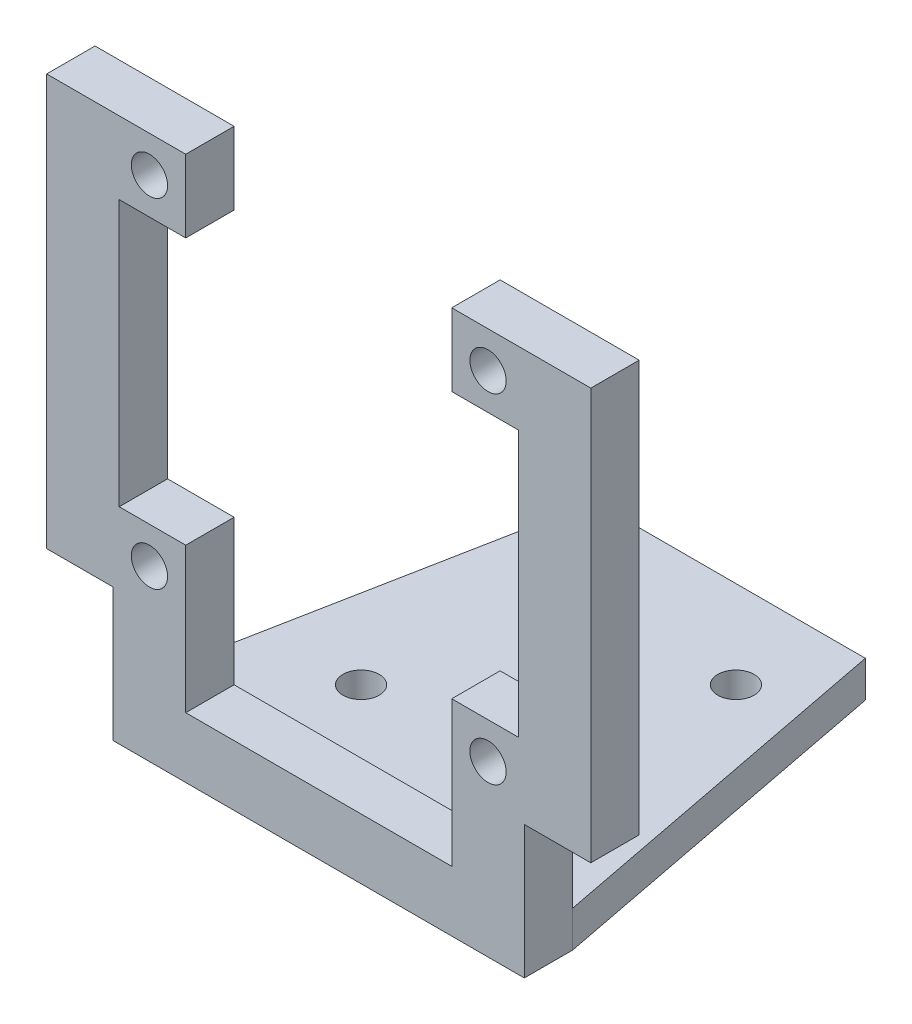
SolidWorks part; units mm, degrees
material "Polyetheretherketone (PEEK)"
ref_plane "Front Plane" through (0, 0, 0) normal (0, 0, 1) x (1, 0, 0)
ref_plane "Top Plane" through (0, 0, 0) normal (0, 1, 0) x (1, 0, 0)
ref_plane "Right Plane" through (0, 0, 0) normal (1, 0, 0) x (0, 0, -1)
sketch "Sketch1" plane through (0, 0, 0) normal (0, 0, 1) x (1, 0, 0)
  line L0 (0, 0) -> (0, 95.25) construction
  line L1 (0, 0) -> (110.5692, 0) construction
  line L2 (11, 17) -> (17, 17)
  line L3 (-17, 17) -> (-11, 17)
  line L4 (-17, 17) -> (-17, -28)
  line L5 (-17, -28) -> (17, -28)
  line L6 (17, 17) -> (17, -28)
  line L12 (-11, 17) -> (-11, -23)
  line L13 (-11, -23) -> (11, -23)
  line L14 (11, 17) -> (11, -23)
  circle A0 centre (-14, 14) radius 1.5
  circle A1 centre (14, 14) radius 1.5
  circle A2 centre (14, -14) radius 1.5
  circle A3 centre (-14, -14) radius 1.5
  dimension "D3" = 3
  dimension "D1" = 34
  dimension "D2" = 45
  dimension "D4" = 28
  dimension "D5" = 14
  dimension "D6" = 28
  dimension "D7" = 5
  dimension "D8" = 22
  dimension "D9" = 14
  dimension "D10" = 28
extrude "Boss-Extrude1" add sketch "Sketch1" along normal blind 4
sketch "Sketch2" plane through (0, 0, 0) normal (0, 0, -1) x (-1, 0, 0)
  line L0 (-17, -28) -> (-17, 17) construction
  line L1 (17, -28) -> (-17, -28)
  line L2 (17, -28) -> (17, -25)
  line L3 (17, -25) -> (-17, -25)
  line L4 (-17, -28) -> (-17, -25)
  dimension "D1" = 3
extrude "Boss-Extrude2" add sketch "Sketch2" along normal blind 30
sketch "Sketch3" plane through (0, -25, 0) normal (0, 1, 0) x (1, 0, 0)
  line L0 (0, 0) -> (0, 39.3383) construction
  line L1 (-17, 15) -> (13.9003, 15) construction
  line L3 (-17, 30) -> (-17, 0) construction
  point P0 (7.75, 22.75)
  dimension "D1" = 15.5
  dimension "D2" = 15.5
hole_wizard "Ø3.0mm Dowel Hole1" positions "Sketch4" profile "Sketch5" hole size "Ø3.0" standard "ISO" end condition through all
sketch "Sketch4" plane through (0, -25, 0) normal (0, 1, 0) x (1, 0, 0)
  point P0 (7.75, 22.75)
sketch "Sketch5" plane through (7.75, -25, -22.75) normal (1, 0, 0) x (0, 0, 1)
  line L0 (0, 0) -> (0, 3)
  line L1 (0, 3) -> (1.5, 3)
  line L2 (1.5, 3) -> (1.5, 0)
  line L5 (1.5, 0) -> (0, 0)
  line L11 (0, -6.35) -> (0, 107.95) construction
  dimension "Thru Hole Dia." = 3
  dimension "Thru Hole Depth" = 3
ref_plane "Plane1" through (0, 0, -15) normal (0, 0, -1) x (-1, 0, 0)
ref_plane "Plane2" through (0, 0, 0) normal (1, 0, 0) x (0, 0, -1)
ref_axis "Axis1" through (0, 19.25, -15) along (0, -1, 0)
pattern_circular "CirPattern1" count 4 over 360 about axis through (0, 19.25, -15) along (0, -1, 0) of "Ø3.0mm Dowel Hole1"
sketch "Sketch6" plane through (0, -25, 0) normal (0, 1, 0) x (1, 0, 0)
  line L0 (17, 0) -> (11.2026, 30)
  line L1 (-17, 30) -> (17, 30) construction
  line L2 (11.2026, 30) -> (17, 30)
  line L3 (17, 30) -> (17, 0)
extrude "Cut-Extrude1" cut sketch "Sketch6" against normal blind 31
mirror "Mirror1" about plane through (0, 0, 0) normal (1, 0, 0) of "Cut-Extrude1"
sketch "Sketch7" plane through (0, 0, 4) normal (0, 0, 1) x (1, 0, 0)
  line L0 (-14, 14) -> (-14, -14) construction
  line L1 (17, 17) -> (22.5, 17)
  line L2 (17, 17) -> (17, -17)
  line L3 (17, -17) -> (22.5, -17)
  line L4 (22.5, 17) -> (22.5, -17)
  line L5 (-14, 0) -> (31.9362, 0) construction
  dimension "D2" = 5.5
extrude "Boss-Extrude3" add sketch "Sketch7" against normal up to surface (4 mm away) up to face at (-12.5, -14, 0)
sketch "Sketch8" plane through (0, 0, 4) normal (0, 0, 1) x (1, 0, 0)
  line L0 (11, 17) -> (11, -23) construction
  line L1 (11, 11) -> (16.5, 11)
  line L2 (11, 11) -> (11, -11)
  line L3 (11, -11) -> (16.5, -11)
  line L4 (16.5, 11) -> (16.5, -11)
  line L5 (0, 0) -> (33.5651, 0) construction
  dimension "D1" = 22
  dimension "D2" = 5.5
extrude "Cut-Extrude2" cut sketch "Sketch8" against normal blind 32
mirror "Mirror2" about plane through (0, 0, 0) normal (1, 0, 0) of "Boss-Extrude3"
mirror "Mirror3" about plane through (0, 0, 0) normal (1, 0, 0) of "Cut-Extrude2"
